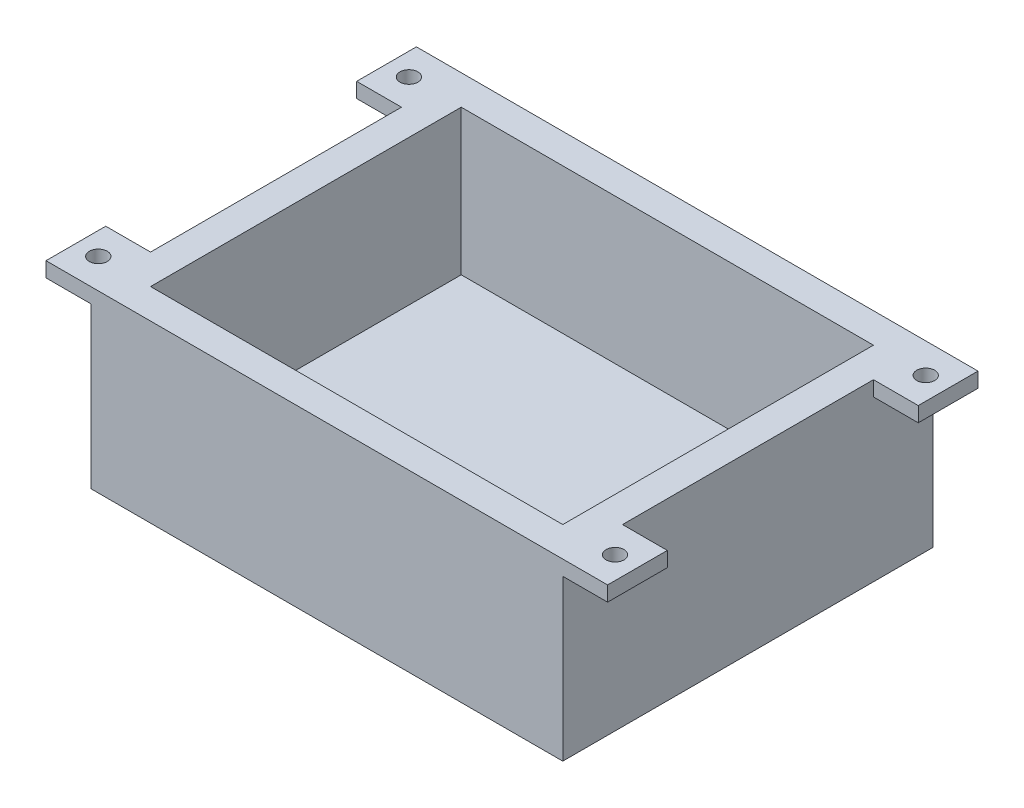
SolidWorks part; units mm, degrees
ref_plane "Front Plane" through (0, 0, 0) normal (0, 0, 1) x (1, 0, 0)
ref_plane "Top Plane" through (0, 0, 0) normal (0, 1, 0) x (1, 0, 0)
ref_plane "Right Plane" through (0, 0, 0) normal (1, 0, 0) x (0, 0, -1)
sketch "Sketch1" plane through (0, 0, 0) normal (0, 1, 0) x (1, 0, 0)
  line L0 (39.5, -31) -> (-39.5, -31)
  line L1 (34.5, -26) -> (-34.5, -26)
  line L2 (34.5, -26) -> (34.5, 26)
  line L3 (34.5, 26) -> (-34.5, 26)
  line L4 (-34.5, -26) -> (-34.5, 26)
  line L5 (34.5, -26) -> (-34.5, 26) construction
  line L6 (34.5, 26) -> (-34.5, -26) construction
  line L7 (-39.5, -31) -> (-39.5, 31)
  line L8 (39.5, 31) -> (-39.5, 31)
  line L9 (39.5, -31) -> (39.5, 31)
  point P0 (0, 0)
  point P10 (0, 0)
  dimension "D1" = 52
  dimension "D2" = 69
  dimension "D3" = 5
extrude "Boss-Extrude1" add sketch "Sketch1" along normal blind 24.3
extrude "Boss-Extrude2" add sketch "Sketch1<2>" against normal blind 5 contours L0 L9 L8 L7 L1 L4 L3 L2 | L4 L1 L2 L3 | L0 L7 L8 L9 region at (0, 0, 29.9958) region at (0, 0, 0)
sketch "Sketch1<2>" plane through (0, 0, 0) normal (0, 1, 0) x (1, 0, 0) same geometry as "Sketch1"
sketch "Sketch3" plane through (-39.5, 0, 0) normal (-1, 0, 0) x (0, 0, 1)
  line L0 (0, 0) -> (0, 24.3) construction
  line L1 (-31, 24.3) -> (-21, 24.3)
  line L2 (-31, 24.3) -> (-31, 21.8)
  line L3 (-31, 21.8) -> (-21, 21.8)
  line L4 (-21, 24.3) -> (-21, 21.8)
  line L5 (-31, 24.3) -> (31, 24.3) construction
  line L6 (31, 21.8) -> (21, 21.8)
  line L7 (21, 24.3) -> (21, 21.8)
  line L8 (31, 24.3) -> (21, 24.3)
  line L9 (31, 24.3) -> (31, 21.8)
  dimension "D1" = 10
  dimension "D2" = 2.5
extrude "Boss-Extrude3" add sketch "Sketch3" along normal blind 7.5
ref_plane "Plane1" through (0, 0, 0) normal (-1, 0, 0) x (0, 0, 1)
mirror "Mirror1" about plane through (0, 0, 0) normal (-1, 0, 0) of "Boss-Extrude3"
sketch "Sketch4" plane through (0, 21.8, 0) normal (0, -1, 0) x (1, 0, 0)
  line L0 (47, 26) -> (39.5, 26) construction
  line L1 (47, 21) -> (47, 31) construction
  line L2 (39.5, 21) -> (39.5, 31) construction
  line L3 (43.25, 31) -> (43.25, 21) construction
  line L4 (47, 31) -> (39.5, 31) construction
  line L5 (47, 21) -> (39.5, 21) construction
  line L6 (0, 0) -> (0, 9.6014) construction
  line L7 (0, 0) -> (-6.5097, 0) construction
  circle A0 centre (43.25, 26) radius 1.5
  circle A1 centre (-43.25, 26) radius 1.5
  circle A2 centre (-43.25, -26) radius 1.5
  circle A3 centre (43.25, -26) radius 1.5
  dimension "D1" = 3
extrude "Cut-Extrude1" cut sketch "Sketch4" against normal through all both and the other way through all
